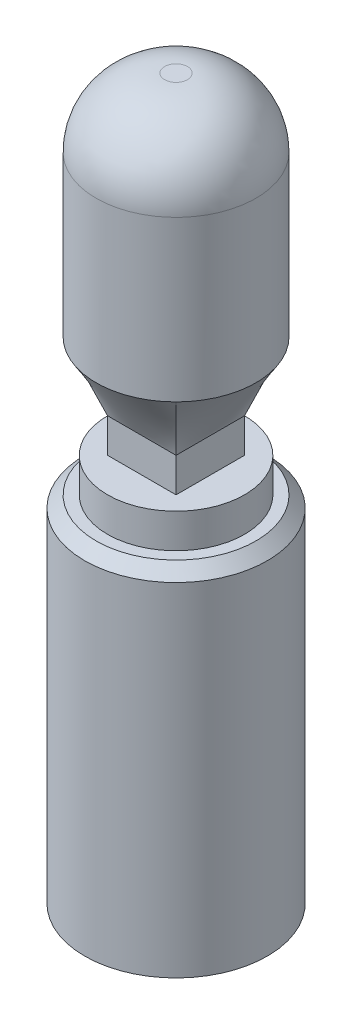
SolidWorks part; units mm, degrees
ref_plane "Front" through (0, 0, 0) normal (0, 0, 1) x (1, 0, 0)
ref_plane "Top" through (0, 0, 0) normal (0, 1, 0) x (1, 0, 0)
ref_plane "Right" through (0, 0, 0) normal (1, 0, 0) x (0, 0, -1)
sketch "Sketch1" plane through (0, 0, 0) normal (0, 1, 0) x (1, 0, 0)
  circle A0 centre (0, 0) radius 8
  dimension "D1" = 16
extrude "Boss-Extrude1" add sketch "Sketch1" along normal blind 30
sketch "Sketch2" plane through (0, 30, 0) normal (0, 1, 0) x (1, 0, 0)
  circle A1 centre (0, 0) radius 8
  circle A2 centre (0, 0) radius 8
  dimension "D1" = 0
extrude "Boss-Extrude2" add sketch "Sketch2" along normal blind 1 draft 45
sketch "Sketch3" plane through (0, 31, 0) normal (0, 1, 0) x (1, 0, 0)
  circle A0 centre (0, 0) radius 6
  dimension "D1" = 12
extrude "Boss-Extrude3" add sketch "Sketch3" along normal blind 3
sketch "Sketch4" plane through (0, 34, 0) normal (0, 1, 0) x (1, 0, 0)
  line L1 (-3, -3) -> (3, -3)
  line L2 (-3, -3) -> (-3, 3)
  line L3 (-3, 3) -> (3, 3)
  line L4 (3, -3) -> (3, 3)
  line L5 (-3, -3) -> (3, 3) construction
  line L6 (-3, 3) -> (3, -3) construction
  point P0 (0, 0)
  dimension "D1" = 6
extrude "Boss-Extrude4" add sketch "Sketch4" along normal blind 3
ref_plane "Plane1" through (0, 43, 0) normal (0, 1, 0) x (1, 0, 0)
sketch "Sketch5" plane through (0, 37, 0) normal (0, 1, 0) x (1, 0, 0)
  line L4 (3, -3) -> (3, 3)
  line L5 (3, 3) -> (-3, 3)
  line L6 (-3, 3) -> (-3, -3)
  line L7 (-3, -3) -> (3, -3)
  line L8 (3, -3) -> (3, 3)
  line L9 (3, 3) -> (-3, 3)
  line L10 (-3, 3) -> (-3, -3)
  line L11 (-3, -3) -> (3, -3)
  dimension "D1" = 0
sketch "Sketch6" plane through (0, 43, 0) normal (0, 1, 0) x (1, 0, 0)
  circle A0 centre (0, 0) radius 7
  dimension "D1" = 14
loft "Loft1" add profiles "Sketch6", "Sketch5" connector at (0, 43, 7) connector at (-3, 37, -3)
sketch "Sketch7" plane through (0, 43, 0) normal (0, 1, 0) x (1, 0, 0)
  arc A4 (4.9497, -4.9497) -> (4.9497, 4.9497) centre (0, 0) ccw
  arc A5 (4.9497, 4.9497) -> (-4.9497, 4.9497) centre (0, 0) ccw
  arc A6 (-4.9497, 4.9497) -> (-4.9497, -4.9497) centre (0, 0) ccw
  arc A7 (-4.9497, -4.9497) -> (4.9497, -4.9497) centre (0, 0) ccw
  arc A8 (4.9497, -4.9497) -> (4.9497, 4.9497) centre (0, 0) ccw
  arc A9 (4.9497, 4.9497) -> (-4.9497, 4.9497) centre (0, 0) ccw
  arc A10 (-4.9497, 4.9497) -> (-4.9497, -4.9497) centre (0, 0) ccw
  arc A11 (-4.9497, -4.9497) -> (4.9497, -4.9497) centre (0, 0) ccw
  dimension "D1" = 0
extrude "Boss-Extrude5" add sketch "Sketch7" along normal blind 20
fillet "Fillet1" radius 6 1 edges at (0, 63, 7)
sketch "Sketch9" plane through (0, 0, 0) normal (0, -1, 0) x (1, 0, 0)
  circle A0 centre (0, 0) radius 2.05
  dimension "D1" = 4.1
extrude "Cut-Extrude1" cut sketch "Sketch9" against normal blind 6
